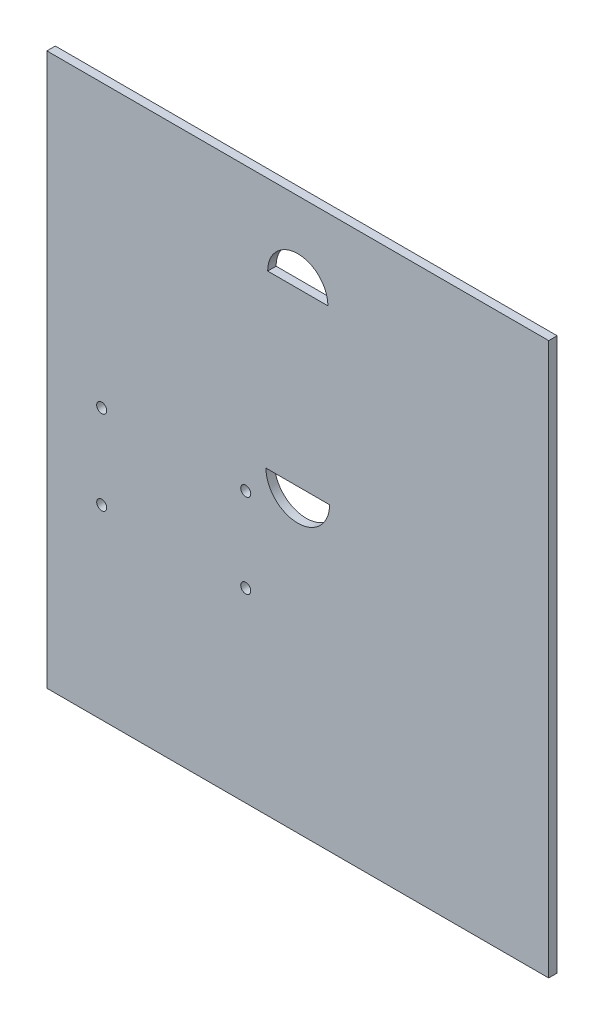
SolidWorks part; units mm, degrees
ref_plane "Plan de face" through (0, 0, 0) normal (0, 0, 1) x (1, 0, 0)
ref_plane "Plan de dessus" through (0, 0, 0) normal (0, 1, 0) x (1, 0, 0)
ref_plane "Plan de droite" through (0, 0, 0) normal (1, 0, 0) x (0, 0, -1)
sketch "Sketch1" plane through (0, 0, 0) normal (0, 0, 1) x (1, 0, 0)
  line L1 (-220.2282, 110.1141) -> (29.7718, 110.1141)
  line L2 (-220.2282, 110.1141) -> (-220.2282, -164.8859)
  line L3 (-220.2282, -164.8859) -> (29.7718, -164.8859)
  line L4 (29.7718, 110.1141) -> (29.7718, -164.8859)
  dimension "D1" = 275
  dimension "D2" = 250
extrude "Boss-Extrude1" add sketch "Sketch1" along normal blind 4.2
sketch "Esquisse1" plane through (0, 0, 4.2) normal (0, 0, 1) x (1, 0, 0)
  line L0 (-220.2282, 110.1141) -> (-220.2282, -164.8859) construction
  line L1 (-110.2282, 70.1141) -> (-80.2282, 70.1141)
  line L2 (29.7718, 110.1141) -> (-220.2282, 110.1141) construction
  line L5 (-111.0739, -15.3059) -> (-79.3825, -15.3059)
  arc A1 (-110.2282, 70.1141) -> (-80.2282, 70.1141) centre (-95.2282, 70.1141) cw
  arc A3 (-111.0739, -15.3059) -> (-79.3825, -15.3059) centre (-95.2282, -15.3059) ccw
  circle A4 centre (-121.1546, -72.134) radius 2.5
  circle A5 centre (-121.1546, -30.224) radius 2.5
  circle A6 centre (-192.9096, -72.134) radius 2.5
  circle A7 centre (-192.9096, -30.224) radius 2.5
  dimension "D2" = 15
  dimension "D4" = 85.42
  dimension "D1" = 125
  dimension "D3" = 40
  dimension "D5" = 0
  dimension "D6" = 41.91
  dimension "D7" = 71.755
  dimension "D8" = 41.91
  dimension "D9" = 71.755
  dimension "D10" = 83.0977
  dimension "D11" = 83.0977
extrude "Enlèv. mat.-Extru.1" cut sketch "Esquisse1" against normal through all
